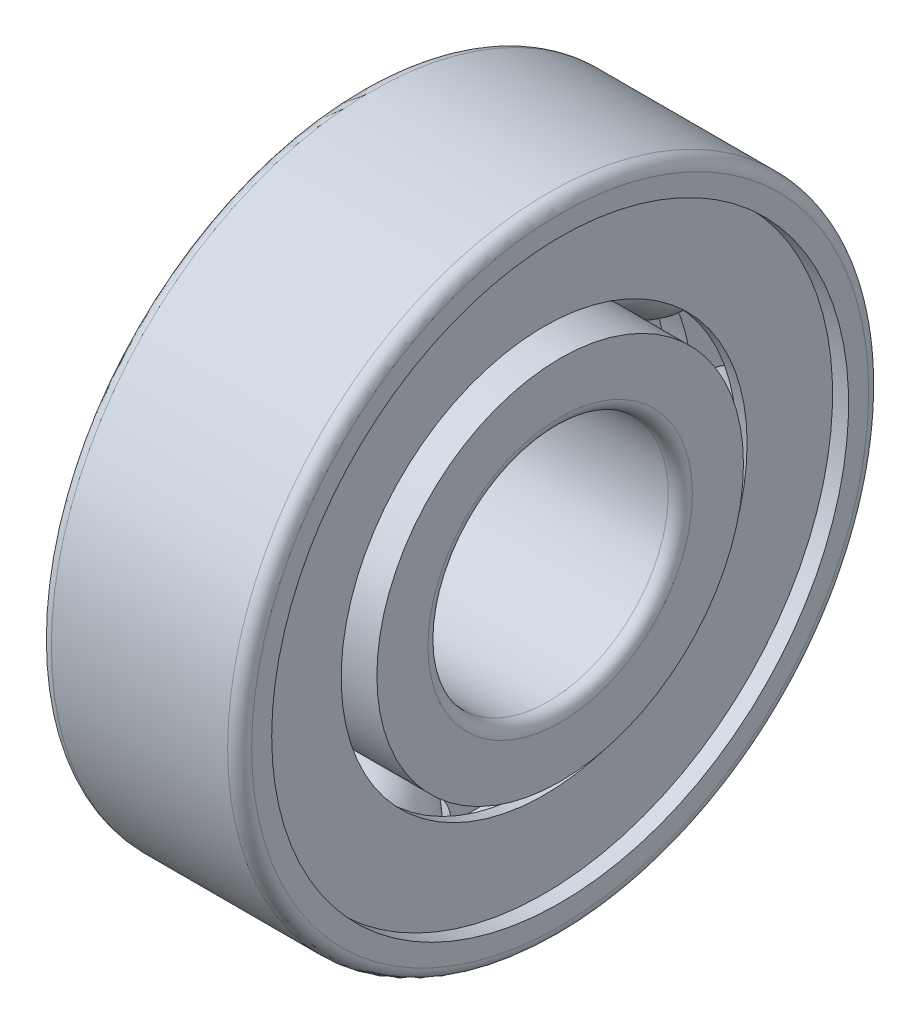
SolidWorks part; units mm, degrees
revolve "凸台-旋转2" add sketch "草图6" angle 360 about L4
sketch "草图6" plane through (0, 0, 0) normal (0, 0, 1) x (1, 0, 0)
  line L0 (0, 0) -> (5.5439, 0) construction
  line L1 (-12.4206, 0) -> (9.8128, 0) construction
  line L2 (0, 0) -> (0, 11.4011) construction
  line L3 (-5.5681, 11.775) -> (6.1049, 11.775) construction
  line L4 (-5.5681, 11.775) -> (6.1049, 11.775) construction
  line L5 (-2.9765, 11.775) -> (2.9765, 11.775)
  arc A0 (-2.9765, 11.775) -> (2.9765, 11.775) centre (0, 11.775) ccw
  dimension "Dw" = 5.953
revolve "基体-旋转" add sketch "草图2" angle 360 about L0
sketch "草图2" plane through (0, 0, 0) normal (0, 0, 1) x (1, 0, 0)
  line L0 (-12.4206, 0) -> (9.8128, 0) construction
  line L1 (0, 0) -> (0, 37.3563) construction
  line L2 (-5.5681, 11.775) -> (6.1049, 11.775) construction
  line L3 (-0.6548, 12.5935) -> (0.6548, 12.5935)
  line L4 (-0.6548, 12.5935) -> (-0.6548, 10.9565)
  line L5 (-0.6548, 10.9565) -> (0.6548, 10.9565)
  line L6 (0.6548, 12.5935) -> (0.6548, 10.9565)
  dimension "D1" = 1.3097
  dimension "D2" = 0.6548
  dimension "D3" = 1.6371
  dimension "D4" = 0.8185
  dimension "D5" = 11.775
revolve "凸台-旋转1" add sketch "草图3" angle 360 about L1
sketch "草图3" plane through (0, 0, 0) normal (0, 0, 1) x (1, 0, 0)
  line L0 (-5.5681, 11.775) -> (6.1049, 11.775) construction
  line L1 (-5.5681, 11.775) -> (6.1049, 11.775) construction
  line L2 (-12.4206, 0) -> (9.8128, 0) construction
  line L3 (-12.4206, 0) -> (9.8128, 0) construction
  line L4 (0, 0) -> (0, 37.3563) construction
  line L5 (0, 0) -> (0, 37.3563) construction
  line L6 (-3.2741, 11.775) -> (3.2741, 11.775)
  arc A0 (-3.2741, 11.775) -> (3.2741, 11.775) centre (0, 11.775) ccw
  dimension "Dwww" = 6.5483
  dimension "D2" = 3.2741
pattern_circular "阵列(圆周)1" count 7 over 360 about axis through (-12.4206, 0, 0) along (1, 0, 0) of "凸台-旋转1"
revolve "凸台-旋转3" add sketch "草图7" angle 360 about L0
sketch "草图7" plane through (0, 0, 0) normal (0, 0, 1) x (1, 0, 0)
  line L0 (0, 0) -> (6.6488, 0) construction
  line L1 (0, 0) -> (0, 16.8954) construction
  line L2 (-4.4, 16) -> (4.4, 16)
  line L3 (-5, 15.4) -> (-5, 14.4)
  line L4 (-5, 14.4) -> (-1.3818, 14.4)
  line L5 (5, 15.4) -> (5, 14.4)
  line L6 (1.3818, 14.4) -> (3.6648, 14.4)
  line L7 (4.2, 14.4) -> (5, 14.4)
  line L8 (3.6648, 14) -> (4.2, 14)
  line L9 (3.6648, 14) -> (3.6648, 14.4)
  line L11 (4.2, 14) -> (4.2, 14.4)
  arc A0 (-4.4, 16) -> (-5, 15.4) centre (-4.4, 15.4) ccw
  arc A1 (4.4, 16) -> (5, 15.4) centre (4.4, 15.4) cw
  arc A2 (2.8617, 12.5935) -> (-2.8617, 12.5935) centre (0, 11.775) ccw construction
  arc A3 (1.4032, 14.4) -> (-0.0003, 8.7985) centre (0, 11.775) ccw construction
  arc A4 (1.3818, 14.4) -> (-1.3818, 14.4) centre (0, 11.775) ccw
  point P10 (-5, 16)
  point P13 (5, 16)
  dimension "D3" = 5
  dimension "D4" = 0.5352
  dimension "D5" = 28
  dimension "D6" = 0.8
  dimension "B" = 10
ref_plane "基准面1" through (0, 0, 0) normal (0, 0, 1) x (1, 0, 0)
ref_plane "基准面2" through (0, 0, 0) normal (0, 1, 0) x (1, 0, 0)
ref_plane "基准面3" through (0, 0, 0) normal (1, 0, 0) x (0, 0, -1)
sketch "尺寸草图" plane through (0, 0, 0) normal (0, 0, 1) x (1, 0, 0)
  point P0 (0, -75.4307)
  point P1 (5.953, -75.4307)
  point P2 (0, 50.7088)
  point P3 (12, 50.7088)
  point P4 (32, 50.7088)
  point P5 (10, 50.7088)
  point P6 (0, -10.9899)
  point P7 (18.3, -10.9899)
  point P8 (28, -10.9899)
  point P9 (0.6, -10.9899)
  point P10 (7, -75.4307)
  dimension "B" = 10
sketch "草图4" plane through (0, 0, 0) normal (0, 0, 1) x (1, 0, 0)
  line L0 (0, 0) -> (8.1272, 0) construction
  line L1 (-12.4206, 0) -> (9.8128, 0) construction
  line L3 (-0.6548, 12.5935) -> (0.6548, 12.5935) construction
  line L4 (-3.2742, 15.8677) -> (3.2741, 15.8677)
  line L5 (-3.2742, 15.8677) -> (-3.2742, 12.5935)
  line L6 (-3.2742, 12.5935) -> (3.2741, 12.5935)
  line L7 (3.2741, 15.8677) -> (3.2741, 12.5935)
revolve "切除-旋转1" cut sketch "草图4" angle 360 about L0
sketch "草图5" plane through (0, 0, 0) normal (0, 0, 1) x (1, 0, 0)
  line L0 (0, 0) -> (8.2665, 0) construction
  line L1 (-12.4206, 0) -> (9.8128, 0) construction
  line L2 (-0.6548, 10.9565) -> (0.6548, 10.9565) construction
  line L3 (-3.2742, 10.9565) -> (3.2741, 10.9565)
  line L4 (-3.2742, 10.9565) -> (-3.2742, 7.6823)
  line L5 (-3.2742, 7.6823) -> (3.2741, 7.6823)
  line L6 (3.2741, 10.9565) -> (3.2741, 7.6823)
revolve "切除-旋转2" cut sketch "草图5" angle 360 about L0
pattern_circular "阵列(圆周)2" count 7 over 360 about axis through (-12.4206, 0, 0) along (1, 0, 0) of "凸台-旋转2"
sketch "草图8" plane through (0, 0, 0) normal (0, 0, 1) x (1, 0, 0)
  line L0 (-12.4206, 0) -> (9.8128, 0) construction
  line L1 (-12.4206, 0) -> (9.8128, 0) construction
  line L2 (5, 15.4) -> (5, 14.4) construction
  line L3 (-5, 9.15) -> (-1.3818, 9.15)
  line L4 (-5, 9.15) -> (-5, 6.6)
  line L5 (-4.4, 6) -> (4.4, 6)
  line L6 (5, 9.15) -> (5, 6.6)
  line L7 (-5, 15.4) -> (-5, 14.4) construction
  line L8 (1.3818, 9.15) -> (5, 9.15)
  arc A0 (-5, 6.6) -> (-4.4, 6) centre (-4.4, 6.6) ccw
  arc A1 (4.4, 6) -> (5, 6.6) centre (4.4, 6.6) ccw
  arc A2 (-2.8617, 10.9565) -> (2.8617, 10.9565) centre (0, 11.775) ccw construction
  arc A3 (-2.8617, 10.9565) -> (2.8617, 10.9565) centre (0, 11.775) ccw construction
  arc A4 (-1.3818, 9.15) -> (1.3818, 9.15) centre (0, 11.775) ccw
  dimension "D1" = 0.6
  dimension "DD" = 12
  dimension "D2" = 0.01
revolve "凸台-旋转4" add sketch "草图8" angle 360 about L1
sketch "草图10" plane through (0, 0, 0) normal (0, 0, 1) x (1, 0, 0)
  line L0 (3.6648, 14.4) -> (3.6648, -14.4) construction
  line L1 (4.2, 14) -> (3.6648, 14)
  line L2 (4.2, 14) -> (4.2, 10.1322)
  line L3 (4.2, 10.1322) -> (3.6648, 10.1322)
  line L4 (3.6648, 14) -> (3.6648, 10.1322)
  line L5 (1.3818, 9.15) -> (5, 9.15) construction
  line L6 (0, 0) -> (-5.3515, 0) construction
  line L7 (-12.4206, 0) -> (9.8128, 0) construction
  dimension "D1" = 0.9822
revolve "凸台-旋转5" add sketch "草图10" angle 360 about L6
sketch "草图11" plane through (0, 0, 0) normal (1, 0, 0) x (0, 0, -1)
  circle A0 centre (0, 0) radius 16
  circle A1 centre (0, 0) radius 16 construction
extrude "切除-拉伸1" cut sketch "草图11" against normal blind 10
mirror "镜向所有1" about plane through (0, 0, 0) normal (1, 0, 0) of bodies 109
equation "\"D5@草图7\" = \"防尘圈径D3@尺寸草图\""
equation "\"Z@阵列(圆周)1\"=\"球数Z@尺寸草图\" "
equation "\"Dw@草图6\"=\"球径DW@尺寸草图\""
equation "\"DD@草图8\"=\"d@尺寸草图\""
equation "\"D@草图7\"=\"DD@尺寸草图\""
equation "\"B@草图7\"=\"B@尺寸草图\" "
equation "\"DD2@草图8\"=\"内圈外径DD2@尺寸草图\""
equation "\"R@草图7\"=\"r@尺寸草图\""
equation "\"D3@草图2\" = 0.25*\"Dwww@草图3\""
equation "\"D4@草图2\" = \"D3@草图2\"/2"
equation "\"Dwww@草图3\" = 1.1*\"Dw@草图6\""
equation "\"D2@草图3\" = 0.5*\"Dwww@草图3\""
equation "\"D1@草图2\" = 0.2*\"Dwww@草图3\""
equation "\"D2@草图2\" = 0.5*\"D1@草图2\""
equation "\"切除位置@草图4\" = \"Dwww@草图3\"/2"
equation "\"D1@阵列(圆周)2\" = \"Z@阵列(圆周)1\""
equation "\"D3@草图7\" = \"B@草图7\" / 2"
equation "\"D1@草图8\" = \"R@草图7\""
equation "\"D2@草图7\" = 0.9*\"D@草图7\""
equation "\"D5@草图2\" = 0.25* ( \"D2@草图7\" + \"DD2@草图8\" )  "
equation "\"D6@草图7\" = 0.08 * \"B@草图7\""
equation "\"D1@草图10\" = 0.15*\"Dwww@草图3\""
